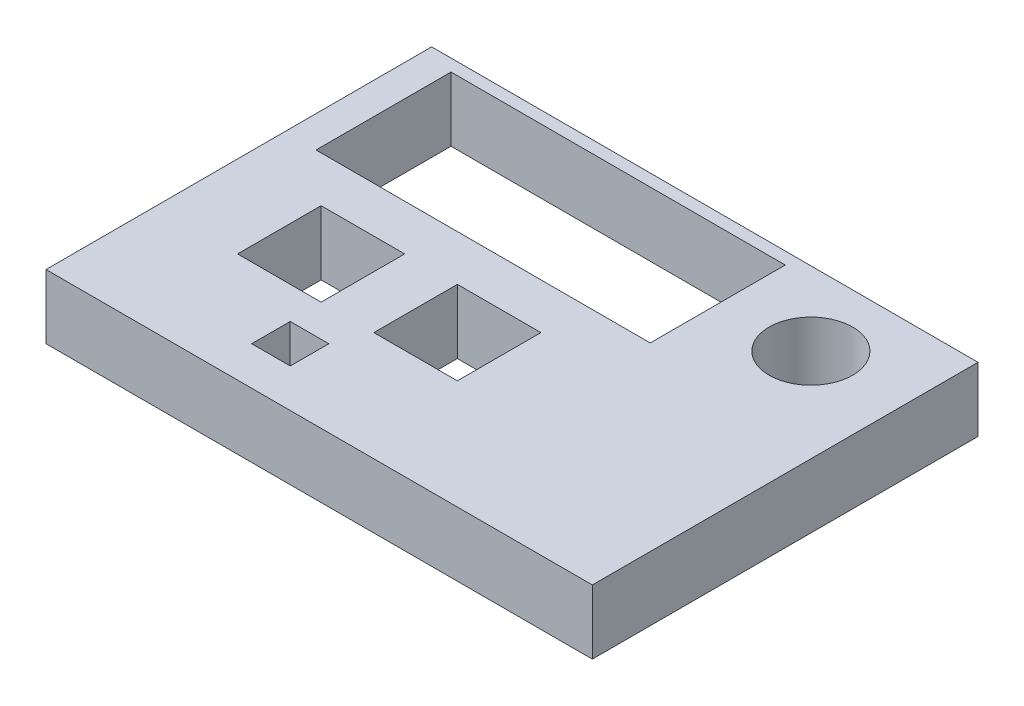
SolidWorks part; units mm, degrees
ref_plane "Front Plane" through (0, 0, 0) normal (0, 0, 1) x (1, 0, 0)
ref_plane "Top Plane" through (0, 0, 0) normal (0, 1, 0) x (1, 0, 0)
ref_plane "Right Plane" through (0, 0, 0) normal (1, 0, 0) x (0, 0, -1)
sketch "Sketch1" plane through (0, 0, 0) normal (0, 1, 0) x (1, 0, 0)
  line L0 (-42.5, -30) -> (-42.5, -13)
  line L1 (-42.5, -30) -> (42.5, -30)
  line L2 (-42.5, -30) -> (-42.5, 30)
  line L3 (-42.5, 30) -> (42.5, 30)
  line L4 (42.5, -30) -> (42.5, 30)
  line L5 (-42.5, -30) -> (42.5, 30) construction
  line L6 (-42.5, 30) -> (42.5, -30) construction
  line L9 (-37.6, 28.11) -> (14.4, 28.11)
  line L10 (-37.6, 28.11) -> (-37.6, 7.11)
  line L11 (-37.6, 7.11) -> (14.4, 7.11)
  line L12 (14.4, 28.11) -> (14.4, 7.11)
  line L13 (-29.7, -13) -> (-16.7, -13)
  line L14 (-29.7, -13) -> (-29.7, 0)
  line L15 (-29.7, 0) -> (-16.7, 0)
  line L16 (-16.7, -13) -> (-16.7, 0)
  line L17 (-8.5, -13) -> (-8.5, 0)
  line L18 (-8.5, 0) -> (4.5, 0)
  line L19 (4.5, 0) -> (4.5, -13)
  line L20 (4.5, -13) -> (-8.5, -13)
  line L21 (-42.5, -30) -> (-13.5, -30)
  line L23 (-13.5, -30) -> (-42.5, -30)
  line L24 (-13.5, -24) -> (-16.5, -24)
  line L25 (-16.5, -24) -> (-16.5, -18)
  line L26 (-16.5, -18) -> (-10.5, -18)
  line L27 (-10.5, -18) -> (-10.5, -24)
  line L28 (-10.5, -24) -> (-13.5, -24)
  circle A0 centre (28, 18.5) radius 6.5
  point P0 (0, 0)
  point P27 (0, 0)
  dimension "D7" = 13
  dimension "D1" = 85
  dimension "D2" = 60
  dimension "D3" = 12.8
  dimension "D4" = 13
  dimension "D5" = 52
  dimension "D6" = 21
  dimension "D8" = 13
  dimension "D9" = 17
  dimension "D10" = 34
  dimension "D11" = 13
  dimension "D12" = 6
  dimension "D14" = 3
  dimension "D15" = 3
  dimension "D16" = 6
extrude "Boss-Extrude1" add sketch "Sketch1" along normal blind 10 contours L1 L4 L3 L2 L0 A0 L16 L13 L14 L15 L9 L12 L11 L10 L19 L20 L17 L18 L27 L28 L24 L25 L26 region at (-41.4596, 0, 21.5)
